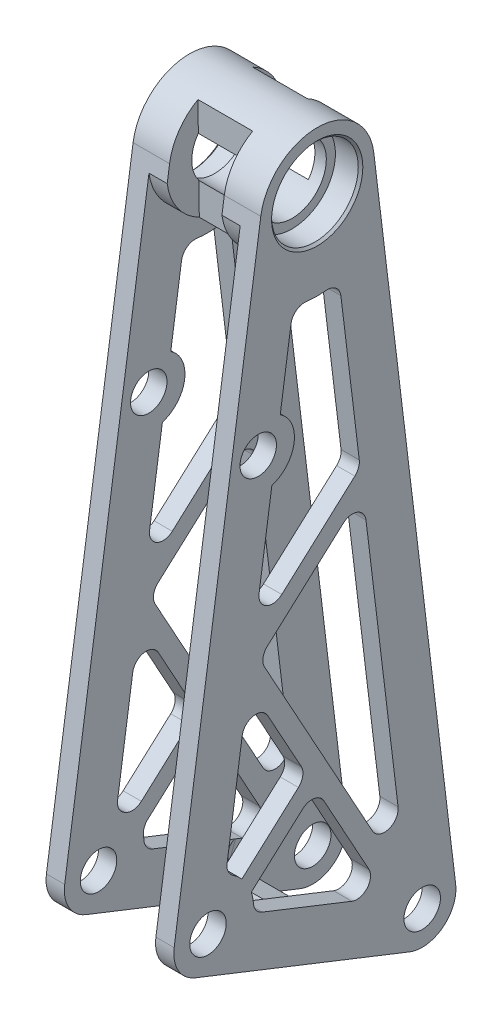
SolidWorks part; units mm, degrees
material "7075-T6 (SN)"
ref_plane "Front Plane" through (0, 0, 0) normal (0, 0, 1) x (1, 0, 0)
ref_plane "Top Plane" through (0, 0, 0) normal (0, 1, 0) x (1, 0, 0)
ref_plane "Right Plane" through (0, 0, 0) normal (1, 0, 0) x (0, 0, -1)
sketch3d "04e FSus"
  line L0 (-536.5, 150, 117) -> (-427, 581, 127)
  line L1 (-427, 581, 127) -> (-236, 150, 142)
  line L2 (-236, 150, 142) -> (-536.5, 150, 117)
  line L3 (-578, 235, 280) -> (-416, 556, 332)
  line L4 (-416, 556, 332) -> (-236, 235, 280)
  line L5 (-236, 235, 280) -> (-578, 235, 280)
  line L6 (-412.5, 542, 156) -> (-412.5, 383, 405)
  line L7 (-490, 573, 155) -> (-490, 160, 151)
  line L8 (-412.5, 383, 405) -> (-412.5, 352, 446)
  line L9 (-412.5, 352, 446) -> (-412.5, 210.5, 587.5)
  line L10 (-490, 573, 155) -> (-420, 543.5, 235)
  line L11 (-420, 543.5, 235) -> (-420, 600, 235)
  line L12 (-412.5, 383, 405) -> (-446, 255, 425)
  line L13 (-446, 255, 425) -> (-380, 255, 425)
  line L14 (-380, 255, 425) -> (-412.5, 383, 405)
  line L15 (-412.5, 352, 446) -> (-446, 255, 425)
  line L16 (-380, 255, 425) -> (-412.5, 352, 446)
  line L17 (-380, -255, 425) -> (-412.5, -352, 446)
  line L18 (-412.5, -352, 446) -> (-446, -255, 425)
  line L19 (-380, -255, 425) -> (-412.5, -383, 405)
  line L20 (-446, -255, 425) -> (-380, -255, 425)
  line L21 (-412.5, -383, 405) -> (-446, -255, 425)
  line L22 (-420, -543.5, 235) -> (-420, -600, 235)
  line L23 (-490, -573, 155) -> (-420, -543.5, 235)
  line L24 (-412.5, -352, 446) -> (-412.5, -210.5, 587.5)
  line L25 (-412.5, -383, 405) -> (-412.5, -352, 446)
  line L26 (-490, -573, 155) -> (-490, -160, 151)
  line L27 (-412.5, -542, 156) -> (-412.5, -383, 405)
  line L28 (-236, -235, 280) -> (-578, -235, 280)
  line L29 (-416, -556, 332) -> (-236, -235, 280)
  line L30 (-578, -235, 280) -> (-416, -556, 332)
  line L31 (-236, -150, 142) -> (-536.5, -150, 117)
  line L32 (-427, -581, 127) -> (-236, -150, 142)
  line L33 (-536.5, -150, 117) -> (-427, -581, 127)
  circle A0 centre (-420, 600, 235) radius 235
  circle A1 centre (-420, -600, 235) radius 235
  point P0 (-536.5, 150, 117)
  point P1 (-236, 150, 142)
  point P2 (-427, 581, 127)
  point P6 (-578, 235, 280)
  point P7 (-236, 235, 280)
  point P8 (-416, 556, 332)
  point P12 (-412.5, 542, 156)
  point P13 (-412.5, 383, 405)
  point P16 (-490, 573, 155)
  point P17 (-490, 160, 151)
  point P20 (-412.5, 210.5, 587.5)
  point P21 (-412.5, 352, 446)
  point P24 (-420, 543.5, 235)
  point P25 (-420, 543.5, 235)
  point P26 (-420, 600, 235)
  point P29 (-446, 255, 425)
  point P30 (-380, 255, 425)
  point P34 (-420, 835, 235)
  point P37 (-420, -835, 235)
ref_plane "Plane1" through (-420, 0, 0) normal (1, 0, 0) x (0, 0, -1)
ref_plane "Plane3" through (0, -600, 0) normal (0, 1, 0) x (1, 0, 0)
ref_plane "Plane5" through (0, -600, 0) normal (0, -1, 0) x (-1, 0, 0)
sketch "Sketch1" plane through (0, 0, 0) normal (0, 0, 1) x (1, 0, 0)
  line L0 (-536.5, 150) -> (-536.5, -150) construction
  line L1 (-536.5, 0) -> (-372.6957, 0) construction
ref_plane "Plane6" through (0, 0, 0) normal (0, 1, 0) x (1, 0, 0)
ref_plane "Plane7" through (-412.5, 0, 0) normal (1, 0, 0) x (0, 0, -1)
sketch "Sketch2" plane through (-412.5, 0, 0) normal (1, 0, 0) x (0, 0, -1)
  line L0 (-401.9884, -402.2742) -> (-425, -255) construction
  line L4 (-425, -255) -> (-448.9429, -383.6173) construction
  line L5 (-448.9429, -383.6173) -> (-401.9884, -402.2742) construction
  line L6 (-425, -255) -> (-401.9884, -402.2742) construction
  line L7 (-448.9429, -383.6173) -> (-425, -255) construction
  line L8 (-401.9884, -402.2742) -> (-448.9429, -383.6173) construction
  line L12 (-456.3633, -382.5275) -> (-437.3673, -253.1837)
  line L13 (-404.707, -409.1562) -> (-451.6985, -390.5927)
  line L14 (-394.6429, -401.3828) -> (-412.5911, -253.494)
  circle A0 centre (-425, -255) radius 7.5
  circle A2 centre (-448.9429, -383.6173) radius 4
  circle A3 centre (-401.9884, -402.2742) radius 4
  arc A9 (-404.707, -409.1562) -> (-394.6429, -401.3828) centre (-401.9884, -402.2742) ccw
  arc A10 (-456.3633, -382.5275) -> (-451.6985, -390.5927) centre (-448.9429, -383.6173) ccw
  arc A12 (-412.5911, -253.494) -> (-437.3673, -253.1837) centre (-425, -255) ccw
  dimension "D1" = 15
  dimension "D4" = 8
  dimension "D5" = 8
  dimension "D32" = 25
extrude "Boss-Extrude1" add sketch "Sketch2" along normal mid plane 28
sketch "Sketch5" plane through (-426.5, 0, 0) normal (-1, 0, 0) x (0, 0, 1)
  circle A1 centre (425, -255) radius 9.5
  dimension "D1" = 19
extrude "Cut-Extrude2" cut sketch "Sketch5" against normal blind 5.5
mirror "Mirror1" about plane through (-412.5, 0, 0) normal (1, 0, 0) of "Cut-Extrude2"
sketch "Sketch6" plane through (-412.5, 0, 0) normal (1, 0, 0) x (0, 0, -1)
  line L0 (-401.9884, -402.2742) -> (-223.6215, -357.0942) construction
  line L1 (-448.9429, -383.6173) -> (-747.0493, -319.2472) construction
  line L2 (-401.9884, -402.2742) -> (-448.9429, -383.6173) construction
  line L3 (-448.9429, -383.6173) -> (-425, -255) construction
  line L4 (-425, -255) -> (-401.9884, -402.2742) construction
  line L5 (-448.9429, -383.6173) -> (-448.9429, -303.8878) construction
  line L7 (-401.9884, -402.2742) -> (-401.9884, -310.3795) construction
  dimension "D2" = 88.36
  dimension "D4" = 84.667
sketch "Sketch7" plane through (-412.5, 0, 0) normal (1, 0, 0) x (0, 0, -1)
  line L0 (-430.742, -276.8924) -> (-444.7578, -372.3264)
  line L1 (-437.0826, -385.4211) -> (-412.1454, -395.2722)
  line L2 (-406.0229, -390.616) -> (-419.8081, -277.0294)
  arc A0 (-427.404, -274.3512) -> (-423.0814, -274.4054) centre (-425, -255) ccw
  circle A1 centre (-425, -255) radius 9.5 construction
  arc A2 (-419.8081, -277.0294) -> (-423.0814, -274.4054) centre (-422.7863, -277.3908) ccw
  arc A3 (-430.742, -276.8924) -> (-427.404, -274.3512) centre (-427.7739, -277.3284) cw
  arc A9 (-443.4404, -375.2673) -> (-444.7578, -372.3264) centre (-441.7897, -372.7623) cw
  arc A10 (-438.9717, -382.8585) -> (-443.4404, -375.2673) centre (-448.9429, -383.6173) ccw
  arc A11 (-438.9717, -382.8585) -> (-437.0826, -385.4211) centre (-435.9804, -382.6309) ccw
  circle A14 centre (-448.9429, -383.6173) radius 4 construction
  arc A15 (-406.0229, -390.616) -> (-412.1454, -395.2722) centre (-401.9884, -402.2742) ccw
  dimension "D2" = 10
  dimension "D4" = 6
  dimension "D1" = 3
  dimension "6" = 6
extrude "Cut-Extrude3" cut sketch "Sketch7" against normal through all and the other way through all
sketch "Sketch8" plane through (-412.5, 0, 0) normal (1, 0, 0) x (0, 0, -1)
  line L3 (-451.6985, -390.5927) -> (-404.707, -409.1562)
  line L4 (-394.6429, -401.3828) -> (-412.5911, -253.494)
  line L5 (-437.3673, -253.1837) -> (-456.3633, -382.5275)
  line L6 (-451.6985, -390.5927) -> (-404.707, -409.1562)
  line L7 (-394.6429, -401.3828) -> (-412.1609, -257.0387)
  line L8 (-437.8862, -256.7165) -> (-456.3633, -382.5275)
  arc A0 (-437.8862, -256.7165) -> (-412.1609, -257.0387) centre (-425, -255) ccw
  arc A3 (-456.3633, -382.5275) -> (-451.6985, -390.5927) centre (-448.9429, -383.6173) ccw
  arc A4 (-404.707, -409.1562) -> (-394.6429, -401.3828) centre (-401.9884, -402.2742) ccw
  arc A5 (-412.5911, -253.494) -> (-437.3673, -253.1837) centre (-425, -255) ccw
  arc A6 (-456.3633, -382.5275) -> (-451.6985, -390.5927) centre (-448.9429, -383.6173) ccw
  arc A7 (-404.707, -409.1562) -> (-394.6429, -401.3828) centre (-401.9884, -402.2742) ccw
  dimension "D2" = 13
  dimension "D1" = 0
extrude "Cut-Extrude4" cut sketch "Sketch8" against normal mid plane 20
sketch "Sketch10" plane through (-412.5, 0, 0) normal (1, 0, 0) x (0, 0, -1)
  line L0 (-428.2043, -391.7131) -> (-422.6239, -393.9176)
  line L1 (-422.6239, -393.9176) -> (-424.461, -398.5679)
  line L2 (-424.461, -398.5679) -> (-430.0413, -396.3634)
  line L3 (-430.0413, -396.3634) -> (-428.2043, -391.7131)
  line L4 (-428.2043, -391.7131) -> (-427.2527, -389.3043) construction
  line L5 (-437.0826, -385.4211) -> (-412.1454, -395.2722) construction
  line L6 (-424.461, -398.5679) -> (-425.4126, -400.9767) construction
  line L7 (-404.707, -409.1562) -> (-451.6985, -390.5927) construction
  line L8 (-427.2512, -397.4656) -> (-428.2027, -399.8745) construction
  dimension "D1" = 5
  dimension "D2" = 6
extrude "Boss-Extrude2" add sketch "Sketch10" along normal mid plane 20
fillet "Fillet2" radius 3 8 edges at (-402.5, -392.8153, 425.4141) (-422.5, -392.8153, 425.4141) (-402.5, -397.4656, 427.2512) (-422.5, -397.4656, 427.2512) (-422.5, -396.2427, 423.5425) (-422.5, -394.0382, 429.1228) (-402.5, -394.0382, 429.1228) (-402.5, -396.2427, 423.5425)
fillet "Fillet3" radius 3 4 edges at (-424.5, -390.616, 406.0229) (-424.5, -395.2722, 412.1454) (-400.5, -390.616, 406.0229) (-400.5, -395.2722, 412.1454)
sketch "Sketch11" plane through (-426.5, 0, 0) normal (-1, 0, 0) x (0, 0, 1)
  line L0 (436.9909, -298.795) -> (434.0228, -299.2309) construction
  line L1 (433.5627, -292.692) -> (435.4622, -305.6261)
  line L2 (430.742, -276.8924) -> (444.7578, -372.3264) construction
  line L3 (434.0228, -299.2309) -> (430.1878, -299.7942) construction
  line L4 (456.3633, -382.5275) -> (437.3673, -253.1837) construction
  circle A6 centre (436.9909, -298.795) radius 4 construction
  arc A8 (433.5627, -292.692) -> (435.4622, -305.6261) centre (436.9909, -298.795) ccw
  dimension "D1" = 14
  dimension "D2" = 8
  dimension "D3" = 7
extrude "Boss-Extrude4" add sketch "Sketch11" against normal up to surface (4 mm away) up to face at (-422.5, -383.6173, 444.9429)
sketch "Sketch12" plane through (-398.5, 0, 0) normal (1, 0, 0) x (0, 0, -1)
  line L1 (-433.5627, -292.692) -> (-435.4622, -305.6261)
  line L2 (-433.5627, -292.692) -> (-435.4622, -305.6261)
  arc A1 (-435.4622, -305.6261) -> (-433.5627, -292.692) centre (-436.9909, -298.795) ccw
  arc A2 (-435.4622, -305.6261) -> (-433.5627, -292.692) centre (-436.9909, -298.795) ccw
  dimension "D1" = 0
extrude "Boss-Extrude5" add sketch "Sketch12" against normal up to surface (4 mm away) up to face at (-402.5, -358.1231, 425.7296)
sketch "Sketch13" plane through (-412.5, 0, 0) normal (1, 0, 0) x (0, 0, -1)
  line L0 (-456.3633, -382.5275) -> (-437.3673, -253.1837) construction
  circle A0 centre (-437.9268, -298.2857) radius 4
  dimension "D1" = 8
  dimension "D2" = 6
extrude "Cut-Extrude5" cut sketch "Sketch13" against normal through all and the other way through all
sketch "Sketch14" plane through (-412.5, 0, 0) normal (1, 0, 0) x (0, 0, -1)
  line L0 (-431.5, -243.7417) -> (-431.25, -244.1747)
  line L1 (-425, -255) -> (-414.5205, -236.849) construction
  line L2 (-425, -255) -> (-435.8073, -273.7188) construction
  line L3 (-425, -255) -> (-413.822, -274.3609) construction
  line L4 (-425, -255) -> (-425, -236.7616) construction
  line L5 (-431.25, -244.1747) -> (-428.75, -248.5048)
  line L6 (-431.5, -266.2583) -> (-428.75, -261.4952)
  line L7 (-421.25, -261.4952) -> (-418.5, -266.2583)
  line L8 (-421.25, -248.5048) -> (-418.5, -243.7417)
  arc A0 (-418.5, -243.7417) -> (-431.5, -243.7417) centre (-425, -255) ccw
  arc A1 (-437.8862, -256.7165) -> (-412.1609, -257.0387) centre (-425, -255) ccw construction
  arc A2 (-428.75, -261.4952) -> (-421.25, -261.4952) centre (-425, -255) ccw
  arc A3 (-412.5911, -253.494) -> (-437.3673, -253.1837) centre (-425, -255) ccw construction
  arc A4 (-431.5, -266.2583) -> (-418.5, -266.2583) centre (-425, -255) ccw
  arc A5 (-421.25, -248.5048) -> (-428.75, -248.5048) centre (-425, -255) ccw
  dimension "D1" = 30
  dimension "D2" = 120
  dimension "D3" = 30
  dimension "D4" = 120
extrude "Cut-Extrude7" [suppressed] cut sketch "Sketch14" against normal mid plane 10
sketch "Sketch15" plane through (-412.5, 0, 0) normal (1, 0, 0) x (0, 0, -1)
  line L0 (-425.1942, -240.2491) -> (-424.8058, -269.7509) construction
  line L1 (-431.1513, -243.5474) -> (-430.8477, -266.6105)
  line L2 (-419.1523, -243.3895) -> (-418.8487, -266.4526)
  line L3 (-431.1937, -240.3281) -> (-430.8053, -269.8299) construction
  line L4 (-419.1947, -240.1701) -> (-418.8063, -269.6719) construction
  arc A0 (-431.1513, -243.5474) -> (-430.8477, -266.6105) centre (-425, -255) ccw
  arc A1 (-437.8862, -256.7165) -> (-412.1609, -257.0387) centre (-425, -255) ccw construction
  arc A2 (-418.8487, -266.4526) -> (-419.1523, -243.3895) centre (-425, -255) ccw
  dimension "D1" = 6
  dimension "D2" = 6
extrude "Cut-Extrude8" cut sketch "Sketch15" against normal mid plane 12
sketch "Sketch16" plane through (-426.5, 0, 0) normal (-1, 0, 0) x (0, 0, 1)
  line L0 (409.4677, -392.4634) -> (440.2034, -336.6703) construction
  line L1 (425, -255) -> (448.9429, -383.6173) construction
  line L2 (440.2034, -336.6703) -> (415.6947, -314.5541) construction
  line L3 (401.9884, -402.2742) -> (425, -255) construction
  line L4 (424.8355, -364.5668) -> (440.3252, -378.5444) construction
  line L5 (407.271, -392.306) -> (437.6869, -337.0934)
  line L6 (437.6869, -337.0934) -> (411.7449, -313.6838)
  line L7 (411.7449, -313.6838) -> (411.0735, -307.6902)
  line L8 (411.0735, -307.6902) -> (442.7199, -336.2472)
  line L9 (442.7199, -336.2472) -> (427.352, -364.1437)
  line L10 (427.352, -364.1437) -> (444.3476, -379.4802)
  line L11 (444.3476, -379.4802) -> (441.3562, -382.1687)
  line L12 (441.3562, -382.1687) -> (425.3695, -367.7426)
  line L13 (425.3695, -367.7426) -> (410.7797, -394.2266)
  line L14 (410.7797, -394.2266) -> (407.271, -392.306)
  arc A0 (410.9076, -393.7513) -> (407.8443, -391.416) centre (401.9884, -402.2742) ccw construction
  arc A1 (443.4404, -375.2673) -> (438.9717, -382.8585) centre (448.9429, -383.6173) ccw construction
  dimension "D1" = 4
  dimension "D2" = 4
  dimension "D3" = 2
  dimension "D4" = 2
  dimension "D5" = 2
  dimension "D6" = 2
  dimension "D7" = 4
extrude "Boss-Extrude6" add sketch "Sketch16" against normal up to surface (4 mm away) up to face at (-422.5, -298.2857, 433.9268)
sketch "Sketch17" plane through (-398.5, 0, 0) normal (1, 0, 0) x (0, 0, -1)
  line L10 (-407.271, -392.306) -> (-437.6869, -337.0934)
  line L11 (-437.6869, -337.0934) -> (-411.7449, -313.6838)
  line L12 (-411.7449, -313.6838) -> (-411.0735, -307.6902)
  line L13 (-411.0735, -307.6902) -> (-442.7199, -336.2472)
  line L14 (-442.7199, -336.2472) -> (-427.352, -364.1437)
  line L15 (-427.352, -364.1437) -> (-444.3476, -379.4802)
  line L16 (-444.3476, -379.4802) -> (-441.3562, -382.1687)
  line L17 (-441.3562, -382.1687) -> (-425.3695, -367.7426)
  line L18 (-425.3695, -367.7426) -> (-410.7797, -394.2266)
  line L19 (-410.7797, -394.2266) -> (-407.271, -392.306)
  line L20 (-407.271, -392.306) -> (-437.6869, -337.0934)
  line L21 (-437.6869, -337.0934) -> (-411.7449, -313.6838)
  line L22 (-411.7449, -313.6838) -> (-411.0735, -307.6902)
  line L23 (-411.0735, -307.6902) -> (-442.7199, -336.2472)
  line L24 (-442.7199, -336.2472) -> (-427.352, -364.1437)
  line L25 (-427.352, -364.1437) -> (-444.3476, -379.4802)
  line L26 (-444.3476, -379.4802) -> (-441.3562, -382.1687)
  line L27 (-441.3562, -382.1687) -> (-425.3695, -367.7426)
  line L28 (-425.3695, -367.7426) -> (-410.7797, -394.2266)
  line L29 (-410.7797, -394.2266) -> (-407.271, -392.306)
  dimension "D1" = 0
extrude "Boss-Extrude7" add sketch "Sketch17" against normal up to surface (4 mm away) up to face at (-402.5, -298.2857, 433.9268)
fillet "Fillet4" radius 3 20 edges at (-424.5, -332.8552, 438.961) (-424.5, -311.7677, 415.5922) (-424.5, -316.6237, 415.0028) (-424.5, -337.0934, 437.6869) (-424.5, -391.3807, 407.7807) (-424.5, -393.8379, 410.9938) (-424.5, -367.7426, 425.3695) (-424.5, -380.4542, 439.4563) (-424.5, -376.9232, 441.514) (-424.5, -364.1437, 427.352) (-424.5, -340.9205, 440.1454) (-400.5, -367.7426, 425.3695) (-400.5, -364.1437, 427.352) (-400.5, -316.6237, 415.0028) (-400.5, -340.9205, 440.1454) (-400.5, -337.0934, 437.6869) (-400.5, -332.8552, 438.961) (-400.5, -393.8379, 410.9938) (-400.5, -391.3807, 407.7807) (-400.5, -311.7677, 415.5922)
chamfer "Chamfer1" distance 0.5 angle 45 2 edges at (-398.5, -255, 434.5) (-426.5, -255, 434.5)
